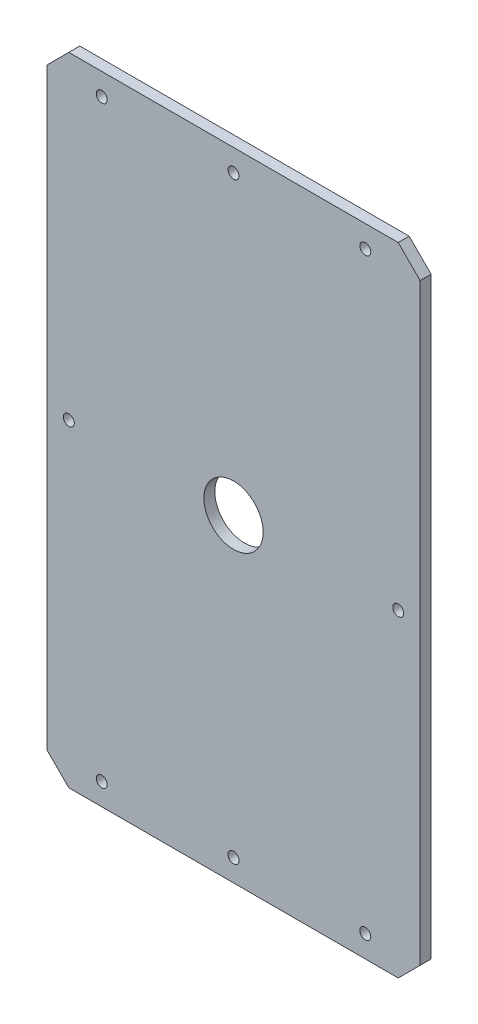
SolidWorks part; units mm, degrees
ref_plane "正面" through (0, 0, 0) normal (0, 0, 1) x (1, 0, 0)
ref_plane "平面" through (0, 0, 0) normal (0, 1, 0) x (1, 0, 0)
ref_plane "右側面" through (0, 0, 0) normal (1, 0, 0) x (0, 0, -1)
sketch "ｽｹｯﾁ1" plane through (0, 0, 0) normal (0, 0, 1) x (1, 0, 0)
  line L1 (-85, 145) -> (85, 145)
  line L2 (-85, 145) -> (-85, -145)
  line L3 (-85, -145) -> (85, -145)
  line L4 (85, 145) -> (85, -145)
  line L5 (-85, 145) -> (85, -145) construction
  line L6 (-85, -145) -> (85, 145) construction
  point P0 (0, 0)
  dimension "D1" = 170
  dimension "D2" = 290
extrude "ﾎﾞｽ - 押し出し1" add sketch "ｽｹｯﾁ1" along normal blind 5
sketch "ｽｹｯﾁ2" plane through (0, 0, 5) normal (0, 0, 1) x (1, 0, 0)
  circle A0 centre (0, 0) radius 13.5
  dimension "D1" = 27
extrude "ｶｯﾄ - 押し出し1" cut sketch "ｽｹｯﾁ2" against normal through all
sketch "ｽｹｯﾁ3" plane through (0, 0, 5) normal (0, 0, 1) x (1, 0, 0)
  line L0 (85, -145) -> (85, 145) construction
  line L1 (-75, 135) -> (75, 135) construction
  line L2 (-75, 135) -> (-75, -135) construction
  line L3 (-75, -135) -> (75, -135) construction
  line L4 (75, 135) -> (75, -135) construction
  line L5 (-75, 135) -> (75, -135) construction
  line L6 (-75, -135) -> (75, 135) construction
  line L7 (85, 145) -> (-85, 145) construction
  line L8 (-85, 0) -> (85, 0) construction
  line L9 (-85, 145) -> (-85, -145) construction
  line L10 (0, 145) -> (0, -145) construction
  line L11 (-85, -145) -> (85, -145) construction
  line L12 (-60, 135) -> (-60, -135) construction
  line L13 (60, 135) -> (60, -135) construction
  circle A0 centre (-75, 0) radius 2.5
  circle A1 centre (0, 135) radius 2.5
  circle A2 centre (75, 0) radius 2.5
  circle A3 centre (0, -135) radius 2.5
  circle A4 centre (-60, 135) radius 2.5
  circle A5 centre (60, 135) radius 2.5
  circle A6 centre (60, -135) radius 2.5
  circle A7 centre (-60, -135) radius 2.5
  point P0 (0, 0)
  dimension "D3" = 5
  dimension "D1" = 10
  dimension "D2" = 10
  dimension "D4" = 60
extrude "ｶｯﾄ - 押し出し2" cut sketch "ｽｹｯﾁ3" against normal through all
chamfer "面取り1" distance 10 angle 45 4 edges at (85, -145, 2.5) (-85, -145, 2.5) (-85, 145, 2.5) (85, 145, 2.5)
